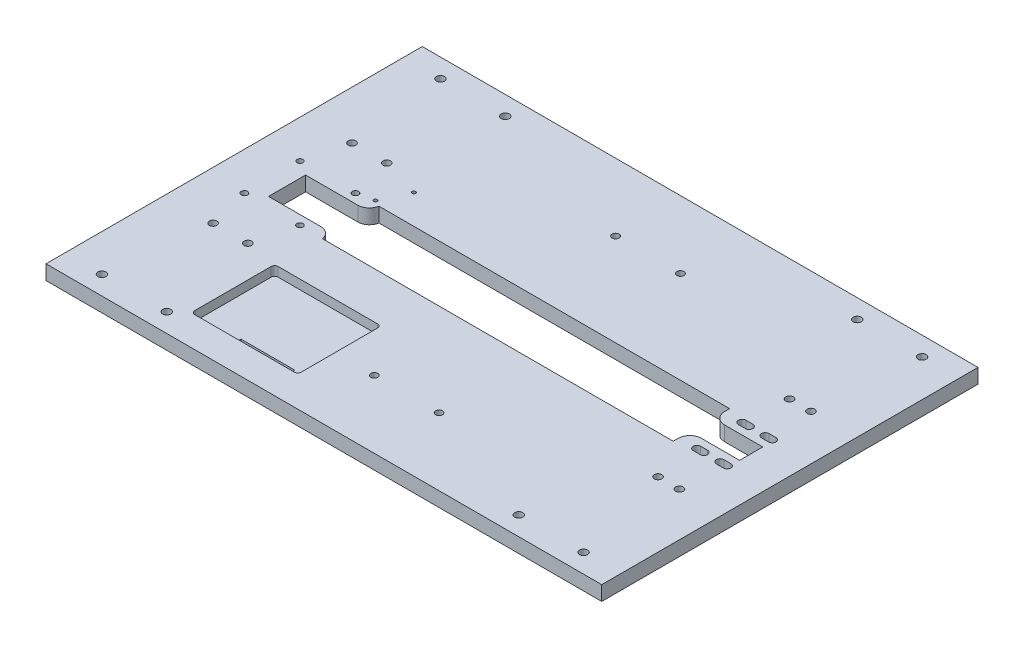
SolidWorks part; units mm, degrees
ref_plane "Front Plane" through (0, 0, 0) normal (0, 0, 1) x (1, 0, 0)
ref_plane "Top Plane" through (0, 0, 0) normal (0, 1, 0) x (1, 0, 0)
ref_plane "Right Plane" through (0, 0, 0) normal (1, 0, 0) x (0, 0, -1)
sketch "Sketch1" plane through (0, 0, 0) normal (0, 1, 0) x (1, 0, 0)
  line L1 (-240, 162.5) -> (240, 162.5)
  line L2 (-240, 162.5) -> (-240, -162.5)
  line L3 (-240, -162.5) -> (240, -162.5)
  line L4 (240, 162.5) -> (240, -162.5)
  line L5 (-240, 162.5) -> (240, -162.5) construction
  line L6 (-240, -162.5) -> (240, 162.5) construction
  point P0 (0, 0)
  dimension "D1" = 480
  dimension "D2" = 325
extrude "Boss-Extrude1" add sketch "Sketch1" along normal blind 12.6
sketch "Sketch2" plane through (0, 0, 0) normal (0, -1, 0) x (1, 0, 0)
  circle A0 centre (41.2474, -104.2) radius 3
  circle A1 centre (-14.7526, -104.2) radius 3
  circle A2 centre (41.2474, 104.2) radius 3
  circle A3 centre (-14.7526, 104.2) radius 3
extrude "Cut-Extrude1" cut sketch "Sketch2" against normal up to next
sketch "Sketch3" plane through (0, 0, 0) normal (0, -1, 0) x (1, 0, 0)
  line L0 (-192.4406, 0) -> (188.5847, 0) construction
  line L1 (163.5847, 24.3647) -> (-139.2887, 24.3647)
  line L2 (163.5847, 24.3647) -> (163.5847, 10)
  line L3 (163.5847, -24.3647) -> (-139.2887, -24.3647)
  line L5 (-139.2887, -24.3647) -> (-139.2887, -16)
  line L6 (-139.2887, -16) -> (-194.2887, -16)
  line L7 (-139.2887, 24.3647) -> (-139.2887, 16)
  line L8 (-139.2887, 16) -> (-194.2887, 16)
  line L9 (-194.2887, 16) -> (-194.2887, -16)
  line L10 (163.5847, 10) -> (206.5847, 10)
  line L11 (206.5847, 10) -> (206.5847, -10)
  line L12 (206.5847, -10) -> (163.5847, -10)
  line L13 (163.5847, -10) -> (163.5847, -24.3647)
  point P0 (0, 0)
  point P1 (-194.2887, 0)
  point P4 (-139.2887, -20.1824)
  dimension "D2" = 55
  dimension "D1" = 16
  dimension "D3" = 10
  dimension "D4" = 10
  dimension "D5" = 43
extrude "Cut-Extrude2" cut sketch "Sketch3" against normal up to next
fillet "Fillet1" radius 10 2 edges at (-139.2887, 6.3, 16) (-139.2887, 6.3, -16)
sketch "Sketch4" plane through (0, 0, 0) normal (0, -1, 0) x (1, 0, 0)
  circle A0 centre (-159.1757, 24) radius 2.6185
  circle A1 centre (-207.1757, 24) radius 2.7
  circle A2 centre (-207.1757, -24) radius 2.5
  circle A3 centre (-159.1757, -24) radius 2.7
  circle A4 centre (-168.1757, -60.0027) radius 3.25
  circle A5 centre (-198.1757, -60.0027) radius 3.25
  circle A6 centre (-168.1757, 60) radius 3.25
  circle A7 centre (-198.1757, 60) radius 3.25
extrude "Cut-Extrude3" cut sketch "Sketch4" against normal up to next
fillet "Fillet2" radius 10 2 edges at (163.5847, 6.3, -10) (163.5847, 6.3, 10)
sketch "Sketch5" plane through (0, 0, 0) normal (0, -1, 0) x (1, 0, 0)
  circle A0 centre (183.6248, 57.5) radius 3.25 construction
  circle A1 centre (202.1353, 57.5) radius 3.25 construction
  circle A2 centre (200.7163, -57.5) radius 3.25 construction
  circle A3 centre (182.2059, -57.5) radius 3.25 construction
  circle A4 centre (183.6248, 57.5) radius 3.25
  circle A5 centre (202.1353, 57.5) radius 3.25
  circle A6 centre (200.7163, -57.5) radius 3.25
  circle A7 centre (182.2059, -57.5) radius 3.25
extrude "Cut-Extrude4" cut sketch "Sketch5" against normal blind 2
extrude "Cut-Extrude5" cut sketch "Sketch5<2>" against normal up to next
sketch "Sketch5<2>" plane through (0, 0, 0) normal (0, -1, 0) x (1, 0, 0) same geometry as "Sketch5"
sketch "Sketch6" plane through (0, 0, 0) normal (0, -1, 0) x (1, 0, 0)
  line L0 (196.0112, -19.5) -> (188.5112, -19.5) construction
  line L1 (196.0112, 19.5) -> (188.5112, 19.5) construction
  line L2 (205.2612, -22.75) -> (199.2612, -22.75)
  line L3 (205.2612, -16.25) -> (199.2612, -16.25)
  line L4 (185.2612, -22.75) -> (179.2612, -22.75)
  line L5 (185.2612, -16.25) -> (179.2612, -16.25)
  line L6 (205.2612, 16.25) -> (199.2612, 16.25)
  line L7 (205.2612, 22.75) -> (199.2612, 22.75)
  line L8 (185.2612, 16.25) -> (179.2612, 16.25)
  line L9 (185.2612, 22.75) -> (179.2612, 22.75)
  line L10 (176.0112, -19.5) -> (171.8318, -19.5) construction
  line L11 (176.0112, 19.5) -> (171.8318, 19.5) construction
  arc A0 (205.2612, -22.75) -> (205.2612, -16.25) centre (205.2612, -19.5) ccw
  arc A1 (185.2612, -22.75) -> (185.2612, -16.25) centre (185.2612, -19.5) ccw
  arc A3 (205.2612, 16.25) -> (205.2612, 22.75) centre (205.2612, 19.5) ccw
  arc A4 (199.2612, -16.25) -> (199.2612, -22.75) centre (199.2612, -19.5) ccw
  arc A7 (179.2612, 22.75) -> (179.2612, 16.25) centre (179.2612, 19.5) ccw
  arc A8 (179.2612, -16.25) -> (179.2612, -22.75) centre (179.2612, -19.5) ccw
  arc A9 (185.2612, 16.25) -> (185.2612, 22.75) centre (185.2612, 19.5) ccw
  arc A10 (199.2612, 22.75) -> (199.2612, 16.25) centre (199.2612, 19.5) ccw
  dimension "D2" = 6.5
  dimension "D3" = 6
  dimension "D7" = 6.5
  dimension "D1" = 6
  dimension "D4" = 6
  dimension "D6" = 6
extrude "Cut-Extrude6" cut sketch "Sketch6" against normal up to next and the other way blind 2
sketch "Sketch7" plane through (0, 12.6, 0) normal (0, 1, 0) x (1, 0, 0)
  circle A0 centre (208, -146.2) radius 2.25
  circle A1 centre (152, -146.2) radius 2.25
  circle A2 centre (-152, -146.2) radius 2.25
  circle A3 centre (-208, -146.2) radius 2.25
  circle A4 centre (-208, 146.2) radius 2.25
  circle A5 centre (-152, 146.2) radius 2.25
  circle A6 centre (208, 146.2) radius 2.25
  circle A7 centre (152, 146.2) radius 2.25
  dimension "D1" = 4.5
extrude "Cut-Extrude7" cut sketch "Sketch7" against normal up to next
sketch "Sketch8" plane through (0, 12.6, 0) normal (0, 1, 0) x (1, 0, 0)
  circle A0 centre (208, 146.2) radius 3.5
  circle A1 centre (152, 146.2) radius 3.5
  circle A2 centre (-152, 146.2) radius 3.5
  circle A3 centre (-208, 146.2) radius 3.5
  circle A4 centre (208, -146.2) radius 3.5
  circle A5 centre (152, -146.2) radius 3.5
  circle A6 centre (-208, -146.2) radius 3.5
  circle A7 centre (-152, -146.2) radius 3.5
  dimension "D1" = 7
extrude "Cut-Extrude8" cut sketch "Sketch8" against normal blind 6
sketch "Sketch9" plane through (0, 12.6, 0) normal (0, 1, 0) x (1, 0, 0)
  line L0 (-139.7386, -65.278) -> (-139.7386, -135.278) construction
  line L1 (-137.7386, -64.278) -> (-51.7386, -64.278)
  line L2 (-140.7386, -67.278) -> (-140.7386, -133.278)
  line L3 (-137.7386, -136.278) -> (-51.7386, -136.278)
  line L4 (-48.7386, -67.278) -> (-48.7386, -133.278)
  line L5 (-49.7386, -135.278) -> (-49.7386, -65.278) construction
  line L6 (-49.7386, -65.278) -> (-139.7386, -65.278) construction
  line L7 (-139.7386, -135.278) -> (-49.7386, -135.278) construction
  arc A0 (-140.7386, -133.278) -> (-137.7386, -136.278) centre (-137.7386, -133.278) ccw
  arc A1 (-51.7386, -136.278) -> (-48.7386, -133.278) centre (-51.7386, -133.278) ccw
  arc A2 (-51.7386, -64.278) -> (-48.7386, -67.278) centre (-51.7386, -67.278) cw
  arc A3 (-137.7386, -64.278) -> (-140.7386, -67.278) centre (-137.7386, -67.278) ccw
  dimension "D5" = 3
  dimension "D1" = 1
  dimension "D2" = 1
  dimension "D3" = 1
  dimension "D4" = 1
extrude "Cut-Extrude9" cut sketch "Sketch9" against normal blind 8
sketch "Sketch10" plane through (0, 4.6, 0) normal (0, 1, 0) x (1, 0, 0)
  line L1 (-107.3842, -126.6207) -> (-60.9487, -126.6207)
  line L2 (-107.3842, -126.6207) -> (-107.3842, -133.6207)
  line L3 (-107.3842, -133.6207) -> (-60.9487, -133.6207)
  line L4 (-60.9487, -126.6207) -> (-60.9487, -133.6207)
  dimension "D1" = 7
extrude "Cut-Extrude10" cut sketch "Sketch10" against normal up to next
sketch "Sketch12" plane through (0, 0, 0) normal (0, -1, 0) x (1, 0, 0)
  circle A0 centre (-145.0986, -27.142) radius 1.5
  circle A1 centre (-134.4986, -49.742) radius 1.5
extrude "Cut-Extrude11" cut sketch "Sketch12" against normal up to next
sketch "Sketch13" plane through (0, 0, 0) normal (0, 1, 0) x (1, 0, 0)
  line L2 (205.2612, 22.75) -> (199.2612, 22.75)
  line L3 (199.2612, 16.25) -> (205.2612, 16.25)
  line L4 (240, -162.5) -> (240, 162.5)
  line L5 (240, 162.5) -> (-240, 162.5)
  line L6 (-240, 162.5) -> (-240, -162.5)
  line L7 (-240, -162.5) -> (240, -162.5)
  line L8 (240, -162.5) -> (240, 162.5)
  line L9 (240, 162.5) -> (-240, 162.5)
  line L10 (-240, 162.5) -> (-240, -162.5)
  line L11 (-240, -162.5) -> (240, -162.5)
  line L12 (205.2612, 22.75) -> (199.2612, 22.75)
  line L13 (199.2612, 16.25) -> (205.2612, 16.25)
  line L14 (205.2612, -16.25) -> (199.2612, -16.25)
  line L15 (199.2612, -22.75) -> (205.2612, -22.75)
  line L16 (205.2612, -16.25) -> (199.2612, -16.25)
  line L17 (199.2612, -22.75) -> (205.2612, -22.75)
  line L18 (163.5847, 20) -> (163.5847, 24.3647)
  line L19 (206.5847, 10) -> (173.5847, 10)
  line L20 (206.5847, -10) -> (206.5847, 10)
  line L21 (173.5847, -10) -> (206.5847, -10)
  line L22 (163.5847, -24.3647) -> (163.5847, -20)
  line L23 (-139.2887, -24.3647) -> (163.5847, -24.3647)
  line L24 (-194.2887, -16) -> (-149.1541, -16)
  line L25 (-194.2887, 16) -> (-194.2887, -16)
  line L26 (-149.1541, 16) -> (-194.2887, 16)
  line L27 (163.5847, 24.3647) -> (-139.2887, 24.3647)
  line L28 (163.5847, 20) -> (163.5847, 24.3647)
  line L29 (206.5847, 10) -> (173.5847, 10)
  line L30 (206.5847, -10) -> (206.5847, 10)
  line L31 (173.5847, -10) -> (206.5847, -10)
  line L32 (163.5847, -24.3647) -> (163.5847, -20)
  line L33 (-139.2887, -24.3647) -> (163.5847, -24.3647)
  line L34 (-194.2887, -16) -> (-149.1541, -16)
  line L35 (-194.2887, 16) -> (-194.2887, -16)
  line L36 (-149.1541, 16) -> (-194.2887, 16)
  line L37 (163.5847, 24.3647) -> (-139.2887, 24.3647)
  line L38 (185.2612, -16.25) -> (179.2612, -16.25)
  line L39 (179.2612, -22.75) -> (185.2612, -22.75)
  line L40 (185.2612, -16.25) -> (179.2612, -16.25)
  line L41 (179.2612, -22.75) -> (185.2612, -22.75)
  line L42 (185.2612, 22.75) -> (179.2612, 22.75)
  line L43 (179.2612, 16.25) -> (185.2612, 16.25)
  line L44 (185.2612, 22.75) -> (179.2612, 22.75)
  line L45 (179.2612, 16.25) -> (185.2612, 16.25)
  line L50 (-137.7386, -136.278) -> (-51.7386, -136.278)
  line L51 (-48.7386, -133.278) -> (-48.7386, -67.278)
  line L52 (-51.7386, -64.278) -> (-137.7386, -64.278)
  line L53 (-140.7386, -67.278) -> (-140.7386, -133.278)
  line L54 (-137.7386, -136.278) -> (-51.7386, -136.278)
  line L55 (-48.7386, -133.278) -> (-48.7386, -67.278)
  line L56 (-51.7386, -64.278) -> (-137.7386, -64.278)
  line L57 (-140.7386, -67.278) -> (-140.7386, -133.278)
  line L58 (-107.3842, -126.6207) -> (-107.3842, -133.6207)
  line L59 (-60.9487, -126.6207) -> (-107.3842, -126.6207)
  line L60 (-60.9487, -133.6207) -> (-60.9487, -126.6207)
  line L61 (-107.3842, -133.6207) -> (-60.9487, -133.6207)
  line L62 (-107.3842, -126.6207) -> (-107.3842, -133.6207)
  line L63 (-60.9487, -126.6207) -> (-107.3842, -126.6207)
  line L64 (-60.9487, -133.6207) -> (-60.9487, -126.6207)
  line L65 (-107.3842, -133.6207) -> (-60.9487, -133.6207)
  circle A0 centre (202.1353, -57.5) radius 3.25 construction
  circle A1 centre (183.6248, -57.5) radius 3.25 construction
  arc A2 (205.2612, 16.25) -> (205.2612, 22.75) centre (205.2612, 19.5) ccw
  arc A3 (199.2612, 22.75) -> (199.2612, 16.25) centre (199.2612, 19.5) ccw
  arc A4 (163.5847, 20) -> (173.5847, 10) centre (173.5847, 20) ccw
  arc A5 (173.5847, -10) -> (163.5847, -20) centre (173.5847, -20) ccw
  arc A6 (-139.2887, -24.3647) -> (-149.1541, -16) centre (-149.1541, -26) ccw
  arc A7 (-149.1541, 16) -> (-139.2887, 24.3647) centre (-149.1541, 26) ccw
  arc A8 (163.5847, 20) -> (173.5847, 10) centre (173.5847, 20) ccw
  arc A9 (173.5847, -10) -> (163.5847, -20) centre (173.5847, -20) ccw
  arc A10 (-139.2887, -24.3647) -> (-149.1541, -16) centre (-149.1541, -26) ccw
  arc A11 (-149.1541, 16) -> (-139.2887, 24.3647) centre (-149.1541, 26) ccw
  arc A12 (205.2612, 16.25) -> (205.2612, 22.75) centre (205.2612, 19.5) ccw
  arc A13 (199.2612, 22.75) -> (199.2612, 16.25) centre (199.2612, 19.5) ccw
  arc A14 (205.2612, -22.75) -> (205.2612, -16.25) centre (205.2612, -19.5) ccw
  arc A15 (199.2612, -16.25) -> (199.2612, -22.75) centre (199.2612, -19.5) ccw
  arc A16 (205.2612, -22.75) -> (205.2612, -16.25) centre (205.2612, -19.5) ccw
  arc A17 (199.2612, -16.25) -> (199.2612, -22.75) centre (199.2612, -19.5) ccw
  arc A18 (185.2612, -22.75) -> (185.2612, -16.25) centre (185.2612, -19.5) ccw
  arc A19 (179.2612, -16.25) -> (179.2612, -22.75) centre (179.2612, -19.5) ccw
  arc A20 (185.2612, -22.75) -> (185.2612, -16.25) centre (185.2612, -19.5) ccw
  arc A21 (179.2612, -16.25) -> (179.2612, -22.75) centre (179.2612, -19.5) ccw
  arc A22 (185.2612, 16.25) -> (185.2612, 22.75) centre (185.2612, 19.5) ccw
  arc A23 (179.2612, 22.75) -> (179.2612, 16.25) centre (179.2612, 19.5) ccw
  arc A24 (185.2612, 16.25) -> (185.2612, 22.75) centre (185.2612, 19.5) ccw
  arc A25 (179.2612, 22.75) -> (179.2612, 16.25) centre (179.2612, 19.5) ccw
  circle A26 centre (182.2059, 57.5) radius 3.25 construction
  circle A27 centre (200.7163, 57.5) radius 3.25 construction
  circle A28 centre (152, -146.2) radius 2.25 construction
  circle A29 centre (152, -146.2) radius 3.5 construction
  circle A30 centre (208, -146.2) radius 2.25 construction
  circle A31 centre (208, -146.2) radius 3.5 construction
  circle A32 centre (41.2474, -104.2) radius 3 construction
  circle A33 centre (-14.7526, -104.2) radius 3 construction
  circle A34 centre (-152, -146.2) radius 2.25 construction
  circle A35 centre (-152, -146.2) radius 3.5 construction
  circle A36 centre (-208, -146.2) radius 2.25 construction
  circle A37 centre (-208, -146.2) radius 3.5 construction
  circle A38 centre (-198.1757, -60) radius 3.25 construction
  circle A39 centre (-168.1757, -60) radius 3.25 construction
  circle A40 centre (-168.1757, -60) radius 3.25
  circle A41 centre (-198.1757, -60) radius 3.25
  circle A42 centre (-208, -146.2) radius 3.5
  circle A43 centre (-208, -146.2) radius 2.25
  circle A44 centre (-152, -146.2) radius 3.5
  circle A45 centre (-152, -146.2) radius 2.25
  circle A46 centre (-14.7526, -104.2) radius 3
  circle A47 centre (41.2474, -104.2) radius 3
  circle A48 centre (208, -146.2) radius 3.5
  circle A49 centre (208, -146.2) radius 2.25
  circle A50 centre (152, -146.2) radius 3.5
  circle A51 centre (152, -146.2) radius 2.25
  circle A52 centre (200.7163, 57.5) radius 3.25
  circle A53 centre (182.2059, 57.5) radius 3.25
  circle A54 centre (183.6248, -57.5) radius 3.25
  circle A55 centre (202.1353, -57.5) radius 3.25
  circle A56 centre (208, 146.2) radius 3.5 construction
  circle A57 centre (208, 146.2) radius 2.25 construction
  circle A58 centre (152, 146.2) radius 3.5 construction
  circle A59 centre (152, 146.2) radius 2.25 construction
  circle A60 centre (41.2474, 104.2) radius 3 construction
  circle A61 centre (-14.7526, 104.2) radius 3 construction
  circle A62 centre (-152, 146.2) radius 3.5 construction
  circle A63 centre (-152, 146.2) radius 2.25 construction
  circle A64 centre (-208, 146.2) radius 3.5 construction
  circle A65 centre (-208, 146.2) radius 2.25 construction
  circle A66 centre (-198.1757, 60.0027) radius 3.25 construction
  circle A67 centre (-168.1757, 60.0027) radius 3.25 construction
  circle A68 centre (-134.4986, 49.742) radius 1.5 construction
  circle A69 centre (-145.0986, 27.142) radius 1.5 construction
  circle A70 centre (-159.1757, 24) radius 2.7 construction
  circle A71 centre (-207.1757, 24) radius 2.5 construction
  circle A72 centre (-207.1757, -24) radius 2.7 construction
  circle A73 centre (-159.1757, -24) radius 2.6185 construction
  circle A74 centre (208, 146.2) radius 3.5
  circle A75 centre (208, 146.2) radius 2.25
  circle A76 centre (152, 146.2) radius 3.5
  circle A77 centre (152, 146.2) radius 2.25
  circle A78 centre (41.2474, 104.2) radius 3
  circle A79 centre (-14.7526, 104.2) radius 3
  circle A80 centre (-152, 146.2) radius 3.5
  circle A81 centre (-152, 146.2) radius 2.25
  circle A82 centre (-208, 146.2) radius 3.5
  circle A83 centre (-208, 146.2) radius 2.25
  circle A84 centre (-198.1757, 60.0027) radius 3.25
  circle A85 centre (-168.1757, 60.0027) radius 3.25
  circle A86 centre (-134.4986, 49.742) radius 1.5
  circle A87 centre (-145.0986, 27.142) radius 1.5
  circle A88 centre (-159.1757, 24) radius 2.7
  circle A89 centre (-207.1757, 24) radius 2.5
  circle A90 centre (-207.1757, -24) radius 2.7
  circle A91 centre (-159.1757, -24) radius 2.6185
  arc A96 (-140.7386, -133.278) -> (-137.7386, -136.278) centre (-137.7386, -133.278) ccw
  arc A97 (-51.7386, -136.278) -> (-48.7386, -133.278) centre (-51.7386, -133.278) ccw
  arc A98 (-48.7386, -67.278) -> (-51.7386, -64.278) centre (-51.7386, -67.278) ccw
  arc A99 (-137.7386, -64.278) -> (-140.7386, -67.278) centre (-137.7386, -67.278) ccw
  arc A100 (-140.7386, -133.278) -> (-137.7386, -136.278) centre (-137.7386, -133.278) ccw
  arc A101 (-51.7386, -136.278) -> (-48.7386, -133.278) centre (-51.7386, -133.278) ccw
  arc A102 (-48.7386, -67.278) -> (-51.7386, -64.278) centre (-51.7386, -67.278) ccw
  arc A103 (-137.7386, -64.278) -> (-140.7386, -67.278) centre (-137.7386, -67.278) ccw
  dimension "D1" = 0
  dimension "D2" = 0
  dimension "D3" = 0
  dimension "D4" = 0
  dimension "D5" = 0
  dimension "D6" = 0
  dimension "D7" = 0
  dimension "D8" = 0
